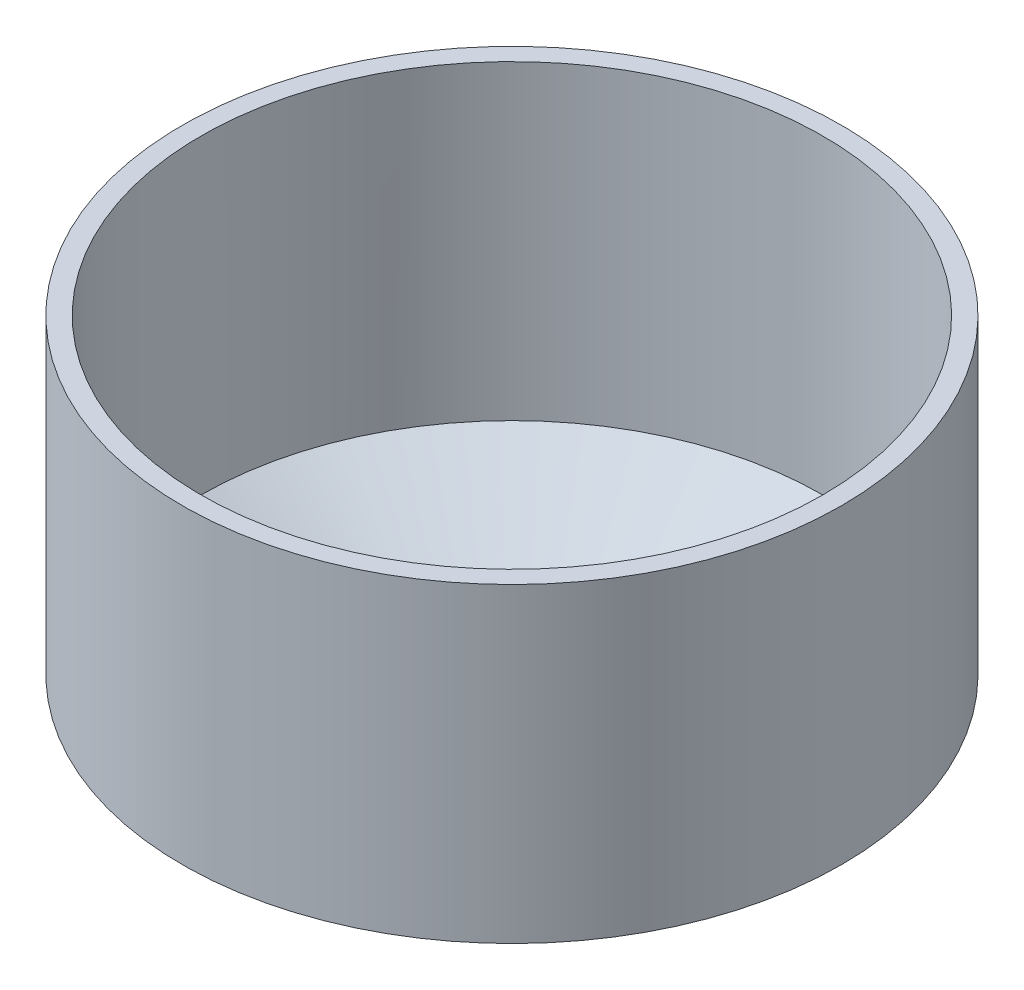
SolidWorks part; units mm, degrees
ref_plane "Front Plane" through (0, 0, 0) normal (0, 0, 1) x (1, 0, 0)
ref_plane "Top Plane" through (0, 0, 0) normal (0, 1, 0) x (1, 0, 0)
ref_plane "Right Plane" through (0, 0, 0) normal (1, 0, 0) x (0, 0, -1)
sketch "Sketch2" plane through (0, 0, 0) normal (0, 0, 1) x (1, 0, 0)
  line L0 (21.2, 20) -> (21.2, 0)
  line L1 (21.2, 0) -> (7.85, -8.2434)
  line L2 (7.85, -8.2434) -> (6.65, -8.2434)
  line L3 (6.65, -8.2434) -> (20, 0)
  line L4 (20, 0) -> (20, 20)
  line L5 (20, 20) -> (21.2, 20)
  line L6 (0, -1000) -> (0, 49000) construction
  dimension "D1" = 1.2
  dimension "D2" = 20
  dimension "D3" = 15.69
  dimension "D4" = 20
  dimension "D5" = 7.85
revolve "Revolve2" add sketch "Sketch2" angle 360 about L6
